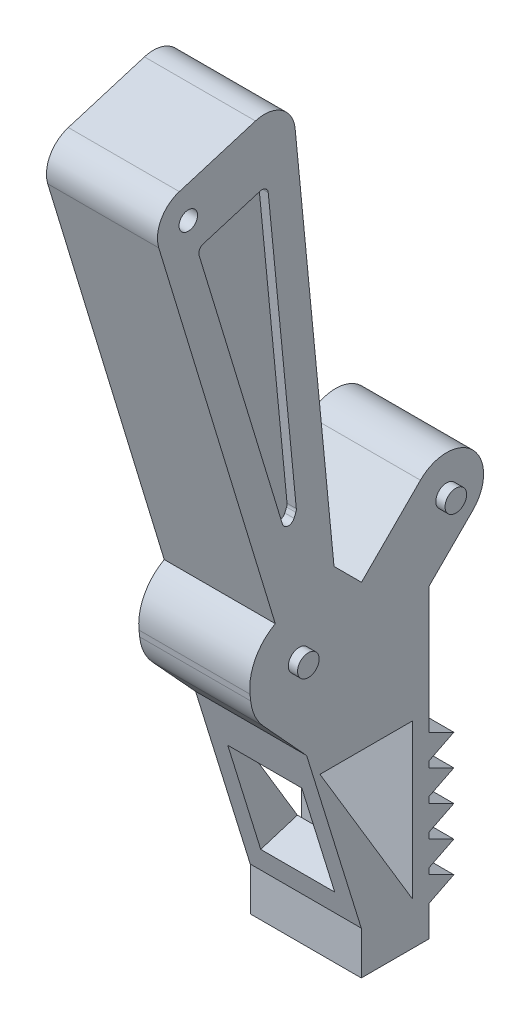
SolidWorks part; units mm, degrees
ref_plane "Front Plane" through (0, 0, 0) normal (0, 0, 1) x (1, 0, 0)
ref_plane "Top Plane" through (0, 0, 0) normal (0, 1, 0) x (1, 0, 0)
ref_plane "Right Plane" through (0, 0, 0) normal (1, 0, 0) x (0, 0, -1)
sketch "Sketch3" plane through (0, 0, 0) normal (1, 0, 0) x (0, 0, -1)
  line L0 (70.136, 0) -> (49.7966, 66.9799)
  line L1 (49.7966, 66.9799) -> (72.7611, 73.9534)
  line L4 (70.136, 0) -> (79.6899, 2.9534)
  line L5 (79.6899, 2.9534) -> (72.7611, 73.9534)
  line L6 (70.136, 0) -> (65.3591, -1.4767)
  line L7 (65.3591, -1.4767) -> (66.4293, -11.4767)
  line L8 (66.4293, -11.4767) -> (75.2179, -21.0559)
  line L9 (75.2179, -21.0559) -> (84.0782, -49.7177)
  line L10 (84.0782, -49.7177) -> (84.0782, -56.7177)
  line L11 (84.0782, -56.7177) -> (95.0782, -56.7177)
  line L12 (95.0782, -56.7177) -> (95.0782, -6.7177)
  line L13 (79.6585, 3.276) -> (84.1104, -1.1759)
  line L15 (95.0782, -7.1787) -> (102.1492, -0.1076)
  line L16 (93.664, 8.3777) -> (84.1104, -1.1759)
  arc A0 (102.1492, -0.1076) -> (93.664, 8.3777) centre (97.9066, 4.1351) ccw
  dimension "D1" = 70
  dimension "D2" = 24
  dimension "D3" = 10
  dimension "D4" = 71
  dimension "D5" = 15
  dimension "D6" = 10
  dimension "D7" = 13
  dimension "D8" = 30
  dimension "D9" = 7
  dimension "D10" = 11
  dimension "D11" = 50
  dimension "D12" = 12
  dimension "D13" = 10
extrude "Boss-Extrude1" add sketch "Sketch3" along normal mid plane 18 contours L15 A0 L16 L13 L5 L4 L6 L7 L8 L9 L10 L11 L12 | L4 L5 L1 L0 region at (0, 40.7083, -67.1584) region at (0, -19.3538, -85.7598)
sketch "Sketch4" plane through (9, 0, 0) normal (1, 0, 0) x (0, 0, -1)
  line L0 (95.0782, -56.7177) -> (95.0782, -7.1787) construction
  line L2 (92.3782, -49.7729) -> (92.3782, -24.7729)
  line L3 (92.3782, -24.7729) -> (77.3782, -24.7729)
  line L4 (77.3782, -24.7729) -> (92.3782, -49.7729)
  dimension "D1" = 15
  dimension "D2" = 25
  dimension "D3" = 2.7
extrude "Cut-Extrude1" cut sketch "Sketch4" against normal blind 25
sketch "Sketch5" plane through (9, 0, 0) normal (1, 0, 0) x (0, 0, -1)
  line L0 (95.0782, -49.7177) -> (99.0782, -49.7177)
  line L1 (95.0782, -56.7177) -> (95.0782, -7.1787) construction
  line L2 (99.0782, -49.7177) -> (95.0782, -51.7177)
  line L3 (99.0782, -49.7177) -> (95.0782, -47.7177)
  line M15 (95.0782, -56.7177) -> (95.0782, -7.1787)
  dimension "D1" = 4
  dimension "D2" = 2
  dimension "D3" = 4
extrude "Boss-Extrude2" add sketch "Sketch5" against normal blind 18 contours L0 L3 M15 | L2 L0 M15 region at (9, -49.051, -96.4115) region at (9, -50.3843, -96.4115)
pattern_linear "LPattern1" count 5 spacing 5 along (0, 1, 0) of "Boss-Extrude2"
fillet "Fillet2" radius 8 2 edges at (0, -11.4767, -66.4293) (0, -1.4767, -65.3591)
fillet "Fillet3" radius 5 2 edges at (0, 73.9534, -72.7611) (0, 66.9799, -49.7966)
sketch "Sketch6" plane through (9, 0, 0) normal (1, 0, 0) x (0, 0, -1)
  circle A0 centre (56.0337, 63.6484) radius 1.5
  dimension "D1" = 3
extrude "Cut-Extrude2" cut sketch "Sketch6" against normal blind 25
sketch "Sketch7" plane through (0, 19.3874, -62.7156) normal (0, -0.2953, 0.9554) x (1, 0, 0)
  line L0 (0, -42.3317) -> (0, -72.3317) construction
  line L1 (9, -42.3317) -> (-9, -42.3317) construction
  line L2 (9, -72.3317) -> (-9, -72.3317) construction
  line L3 (-6, -49.8317) -> (6, -49.8317)
  line L4 (6, -49.8317) -> (6, -67.9263)
  line L5 (6, -67.9263) -> (-6, -67.9263)
  line L6 (-6, -67.9263) -> (-6, -49.8317)
  line L7 (9, -42.3317) -> (9, -72.3317) construction
  line L9 (-9, -42.3317) -> (-9, -72.3317) construction
  dimension "D1" = 7.5
  dimension "D2" = 3
  dimension "D3" = 12
  dimension "D4" = 3
  dimension "D5" = 6
extrude "Cut-Extrude3" cut sketch "Sketch7" against normal blind 8
sketch "Sketch8" plane through (9, 0, 0) normal (1, 0, 0) x (0, 0, -1)
  circle A0 centre (97.9066, 4.1351) radius 1.75
  dimension "D1" = 3.5
extrude "Boss-Extrude3" add sketch "Sketch8" along normal blind 1.5 contours A0
sketch "Sketch12" plane through (9, 0, 0) normal (1, 0, 0) x (0, 0, -1)
  circle A0 centre (73.9966, -7.0068) radius 1.75
  dimension "D1" = 3.5
extrude "Boss-Extrude4" add sketch "Sketch12" along normal blind 1.5
sketch "Sketch13" plane through (9, 0, 0) normal (1, 0, 0) x (0, 0, -1)
  line L0 (73.1731, 13.2749) -> (73.4671, 13.9556)
  line L27 (68.991, 61.1075) -> (73.5443, 14.4492)
  line L28 (57.7771, 57.9073) -> (71.2982, 13.3808)
  line L30 (58.4433, 59.1547) -> (67.7051, 61.9672)
  line L32 (79.6585, 3.276) -> (73.3536, 67.8824) construction
  line L33 (70.136, 0) -> (51.2494, 62.1956) construction
  line L34 (54.5809, 68.4327) -> (66.9244, 72.181) construction
  arc A2 (68.991, 61.1075) -> (67.7051, 61.9672) centre (67.9957, 61.0104) ccw
  arc A3 (57.7771, 57.9073) -> (58.4433, 59.1547) centre (58.7339, 58.1979) cw
  arc A4 (73.5443, 14.4492) -> (73.4671, 13.9556) centre (72.549, 14.3521) cw
  arc A5 (71.2982, 13.3808) -> (73.1731, 13.2749) centre (72.255, 13.6714) ccw
  dimension "D1" = 1
  dimension "D2" = 1
  dimension "D3" = 5
  dimension "D4" = 5
  dimension "D5" = 10
extrude "Cut-Extrude6" cut sketch "Sketch13" against normal blind 1.5 contours A3 L28 L27 A2 L30 region at (9, 42.1931, -66.8125)
ref_plane "Plane1" through (0, 0, 0) normal (1, 0, 0) x (0, 0, -1)
mirror "Mirror1" about plane through (0, 0, 0) normal (1, 0, 0) of "Boss-Extrude3", "Boss-Extrude4", "Cut-Extrude6"
